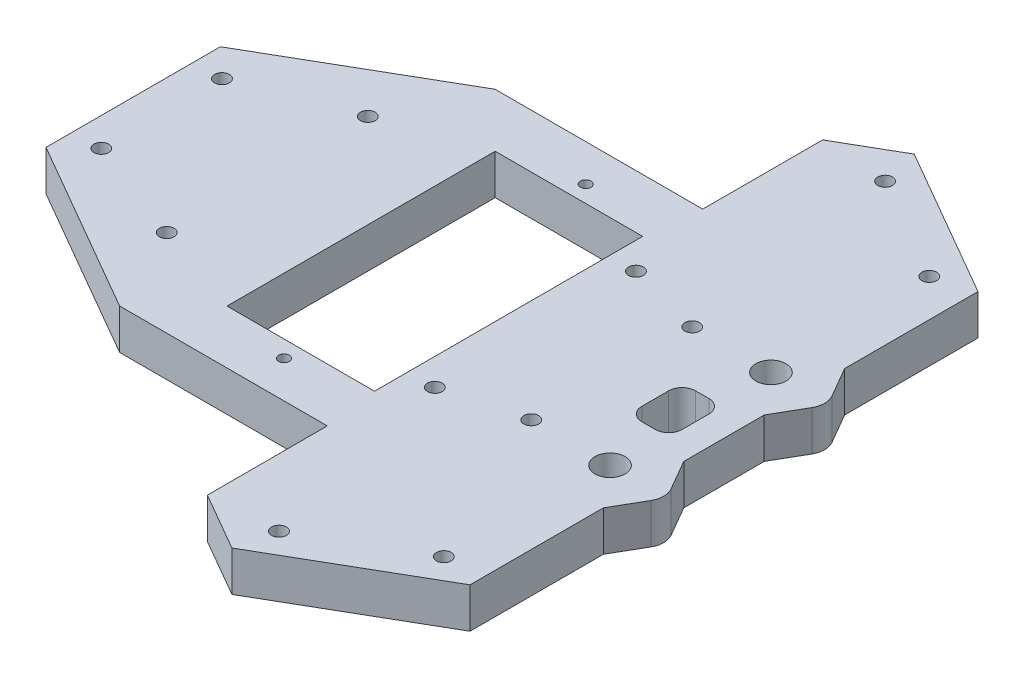
SolidWorks part; units mm, degrees
material "Acrylic (Medium-high impact)"
ref_plane "Front Plane" through (0, 0, 0) normal (0, 0, 1) x (1, 0, 0)
ref_plane "Top Plane" through (0, 0, 0) normal (0, 1, 0) x (1, 0, 0)
ref_plane "Right Plane" through (0, 0, 0) normal (1, 0, 0) x (0, 0, -1)
sketch "Sketch1" plane through (0, 0, 0) normal (0, 1, 0) x (1, 0, 0)
  line L0 (4.75, -20) -> (-17.25, -20)
  line L1 (-17.25, -20) -> (-17.25, 20)
  line L2 (-17.25, 20) -> (4.75, 20)
  line L3 (25.625, 44.3838) -> (23.5, 40.7032) construction
  line L4 (0, 0) -> (23.5, -40.7032) construction
  line L5 (0, 0) -> (-47, 0) construction
  line L6 (4.75, 20) -> (4.75, -20)
  line L7 (14.3667, 50.8838) -> (36.8833, 37.8838)
  line L8 (31.8833, 12) -> (31.8833, -12) construction
  line L9 (15.7058, 45.2032) -> (31.2942, 36.2032) construction
  line L10 (31.2942, -36.2032) -> (15.7058, -45.2032) construction
  line L11 (-47, 9) -> (-47, -9) construction
  line L12 (23.5, 40.7032) -> (0, 0) construction
  line L13 (23.5, -40.7032) -> (25.625, -44.3838) construction
  line L14 (-47, 0) -> (-51.25, 0) construction
  line L15 (0, 0) -> (31.8833, 0) construction
  line L16 (36.8833, 37.8838) -> (36.8833, -37.8838)
  line L17 (36.8833, -37.8838) -> (14.3667, -50.8838)
  line L22 (-51.25, 13) -> (-51.25, -13)
  line L23 (14.3667, 50.8838) -> (5.7064, 45.8838)
  line L24 (14.3667, -50.8838) -> (5.7064, -45.8838)
  line L25 (5.7064, 45.8838) -> (5.7064, 28)
  line L26 (5.7064, 28) -> (-25.2692, 28)
  line L27 (-25.2692, 28) -> (-51.25, 13)
  line L28 (5.7064, -45.8838) -> (5.7064, -28)
  line L29 (5.7064, -28) -> (-25.2692, -28)
  line L30 (-25.2692, -28) -> (-51.25, -13)
  line L69 (25.7064, -23.5) -> (25.7064, 0) construction
  line L70 (25.7064, 0) -> (25.7064, 23.5) construction
  line L71 (26.6333, -4) -> (32.6333, -4)
  line L72 (26.6333, -4) -> (26.6333, 4)
  line L73 (26.6333, 4) -> (32.6333, 4)
  line L74 (32.6333, -4) -> (32.6333, 4)
  line L75 (26.6333, -4) -> (32.6333, 4) construction
  line L76 (26.6333, 4) -> (32.6333, -4) construction
  circle A0 centre (15.7058, 45.2032) radius 1.1
  circle A1 centre (31.2942, 36.2032) radius 1.1
  circle A2 centre (31.2942, -36.2032) radius 1.1
  circle A3 centre (15.7058, -45.2032) radius 1.1
  circle A4 centre (-47, 9) radius 1.1
  circle A5 centre (-47, -9) radius 1.1
  circle A7 centre (15.7058, 45.2032) radius 2.5 construction
  point P4 (-18.25, 0)
  point P28 (-47.0472, 7.3976)
  point P85 (0, 0)
  point P92 (4.75, 0)
  point P93 (0, 0)
  point P114 (29.6333, 0)
  point P148 (0, 0)
  dimension "D2" = 2.2
  dimension "D7" = 5
  dimension "D9" = 26
  dimension "D11" = 47
  dimension "D12" = 5
  dimension "D13" = 34
  dimension "D10" = 56
  dimension "D1" = 18
  dimension "D3" = 4.25
  dimension "D4" = 120
  dimension "D5" = 40
  dimension "D6" = 22
  dimension "D15" = 10
  dimension "D22" = 51.25
  dimension "D33" = 8
  dimension "D34" = 6
  dimension "D35" = 7.25
extrude "Boss-Extrude1" add sketch "Sketch1" along normal blind 6
sketch "Sketch10" plane through (0, 0, 0) normal (0, -1, 0) x (1, 0, 0)
  line L0 (-6.25, 22.5) -> (-6.25, -22.5) construction
  line L1 (4.75, 20) -> (4.75, -20) construction
  line L2 (4.75, -20) -> (-17.25, -20) construction
  point P4 (4.75, 0)
  point P5 (-6.25, 0)
  point P8 (-6.25, -20)
  dimension "D1" = 45
hole_wizard "Ø1.6 (1.6) Diameter Hole3" positions "3DSketch1" profile "Sketch11" hole size "Ø1.6" standard "ISO" end condition through all
sketch3d "3DSketch1"
  point P0 (-6.25, 0, 22.5)
  point P3 (-6.25, 0, -22.5)
sketch "Sketch11" plane through (-6.25, 0, 22.5) normal (1, 0, 0) x (0, 0, -1)
  line L0 (0, 0) -> (0, 6)
  line L1 (0, 6) -> (0.8, 6)
  line L2 (0.8, 6) -> (0.8, 0)
  line L5 (0.8, 0) -> (0, 0)
  line L11 (0, -6.35) -> (0, 107.95) construction
  dimension "Thru Hole Dia." = 1.6
  dimension "Thru Hole Depth" = 6
sketch "Sketch9" plane through (0, 0, 0) normal (0, -1, 0) x (1, 0, 0)
  line L0 (33.0083, -12) -> (30.7583, -12) construction
  line L1 (36.8833, 37.8838) -> (36.8833, -37.8838) construction
  line L2 (39.4814, 13.5) -> (36.8833, 18)
  line L3 (39.4814, 10.5) -> (36.8833, 6)
  line L4 (33.0083, 12) -> (30.7583, 12) construction
  line L5 (36.8833, 0) -> (0, 0) construction
  line L6 (36.8833, -18) -> (36.8833, -6)
  line L7 (39.4814, -10.5) -> (36.8833, -6)
  line L8 (39.4814, -13.5) -> (36.8833, -18)
  line L12 (36.8833, 18) -> (36.8833, 6)
  arc A0 (36.8833, 9) -> (36.8833, 15) centre (36.8833, 12) ccw
  arc A3 (36.8833, -9) -> (36.8833, -15) centre (36.8833, -12) cw
  dimension "D1" = 6
  dimension "D2" = 6
  dimension "D3" = 6
extrude "Boss-Extrude2" add sketch "Sketch9" against normal up to surface (6 mm away) contours A3 L6 | L6 A3 L7 | L8 A3 L6 | L12 A0 | A0 L12 L3 | A0 L2 L12 region at (37.6134, 0, 15.7936) region at (38.1566, 0, 12) region at (37.6134, 0, 8.2064) region at (37.6134, 0, -15.7936) region at (38.1566, 0, -12) region at (37.6134, 0, -8.2064) up to face at (-6.25, 6, 21.7)
fillet "Fillet1" radius 2 4 edges at (26.6333, 3, -4) (26.6333, 3, 4) (32.6333, 3, 4) (32.6333, 3, -4)
sketch "Sketch13" plane through (0, 6, 0) normal (0, 1, 0) x (1, 0, 0)
  line L0 (20.1333, 12) -> (20.1333, -12) construction
  line L1 (20.1333, 0) -> (34.6333, 0) construction
  line L2 (26.6333, 2) -> (26.6333, -2) construction
  line L3 (36.8833, -6) -> (36.8833, 6) construction
  line L4 (39.8833, 12) -> (31.8833, 12) construction
  line L5 (39.8833, -12) -> (31.8833, -12) construction
  arc A1 (39.4814, 10.5) -> (39.4814, 13.5) centre (36.8833, 12) ccw construction
  point P7 (26.6333, 0)
  dimension "D1" = 24
  dimension "D2" = 2.25
  dimension "D3" = 14.5
  dimension "D4" = 8
hole_wizard "Ø2.2 (2.2) Diameter Hole1" positions "3DSketch2" profile "Sketch14" hole size "Ø2.2" standard "ISO" end condition through all
sketch3d "3DSketch2"
  point P0 (20.1333, 6, -12)
  point P6 (20.1333, 6, 12)
sketch "Sketch14" plane through (20.1333, 6, -12) normal (1, 0, 0) x (0, 0, 1)
  line L0 (0, 0) -> (0, 6)
  line L1 (0, 6) -> (1.1, 6)
  line L2 (1.1, 6) -> (1.1, 0)
  line L5 (1.1, 0) -> (0, 0)
  line L11 (0, -6.35) -> (0, 107.95) construction
  dimension "Thru Hole Dia." = 2.2
  dimension "Thru Hole Depth" = 6
hole_wizard "Ø4.0mm Dowel Hole1" positions "3DSketch3" profile "Sketch15" hole size "Ø4.0" standard "ANSI Metric" end condition through all
sketch3d "3DSketch3"
  point P0 (31.8833, 6, -12)
  point P3 (31.8833, 6, 12)
sketch "Sketch15" plane through (31.8833, 6, -12) normal (1, 0, 0) x (0, 0, 1)
  line L0 (0, 0) -> (0, 6)
  line L1 (0, 6) -> (2.25, 6)
  line L2 (2.25, 6) -> (2.25, 0)
  line L5 (2.25, 0) -> (0, 0)
  line L11 (0, -6.35) -> (0, 107.95) construction
  dimension "Thru Hole Dia." = 4.5
  dimension "Thru Hole Depth" = 6
sketch "Dimensions" plane through (0, 6, 0) normal (0, 1, 0) x (1, 0, 0)
  line L0 (8.344, 0) -> (-110.844, 0)
  line L1 (20.1333, 0) -> (34.6333, 0) construction
  line L2 (53.736, 93.0735) -> (-2.486, -4.3059)
  line L4 (-1.5108, 2.6167) -> (52.7608, -91.3843)
  line L8 (36.8833, 6) -> (36.8833, -6)
  line L10 (14.3667, 50.8838) -> (36.8833, 37.8838)
  line L11 (-51.25, 13) -> (-51.25, -13)
  line L12 (14.3667, -50.8838) -> (36.8833, -37.8838)
  point P3 (-51.25, 0)
  point P7 (25.625, 44.3838)
  point P10 (25.625, -44.3838)
  dimension "D1" = 51.25
  dimension "D2" = 25.625
  dimension "D3" = 36.8833
  dimension "D4" = 51.25
  dimension "D5" = 51.25
  dimension "D6" = 51.25
  dimension "D7" = 88.7676
  dimension "D8" = 60
ref_point "Point1"
ref_axis "Axis1" through (0, 6, 0) along (0, 1, 0)
sketch "Sketch16" plane through (0, 6, 0) normal (0, 1, 0) x (1, 0, 0)
  line L1 (-31.25, -15) -> (8.75, -15)
  line L2 (-31.25, -15) -> (-31.25, 15)
  line L3 (-31.25, 15) -> (8.75, 15)
  line L4 (8.75, -15) -> (8.75, 15)
  line L5 (-31.25, 0) -> (8.75, 0) construction
  line L6 (8.344, 0) -> (-110.844, 0) construction
  line L7 (-17.25, 20) -> (-17.25, -20) construction
  dimension "D1" = 40
  dimension "D2" = 30
  dimension "D3" = 14
hole_wizard "Ø2.0mm Dowel Hole1" positions "3DSketch4" profile "Sketch18" hole size "Ø2.0" standard "ANSI Metric" end condition through all
sketch3d "3DSketch4"
  point P0 (-31.25, 6, -15)
  point P3 (-31.25, 6, 15)
  point P6 (8.75, 6, 15)
  point P9 (8.75, 6, -15)
sketch "Sketch18" plane through (-31.25, 6, -15) normal (1, 0, 0) x (0, 0, 1)
  line L0 (0, 0) -> (0, 6)
  line L1 (0, 6) -> (1.1, 6)
  line L2 (1.1, 6) -> (1.1, 0)
  line L5 (1.1, 0) -> (0, 0)
  line L11 (0, -6.35) -> (0, 107.95) construction
  dimension "Thru Hole Dia." = 2.2
  dimension "Thru Hole Depth" = 6
